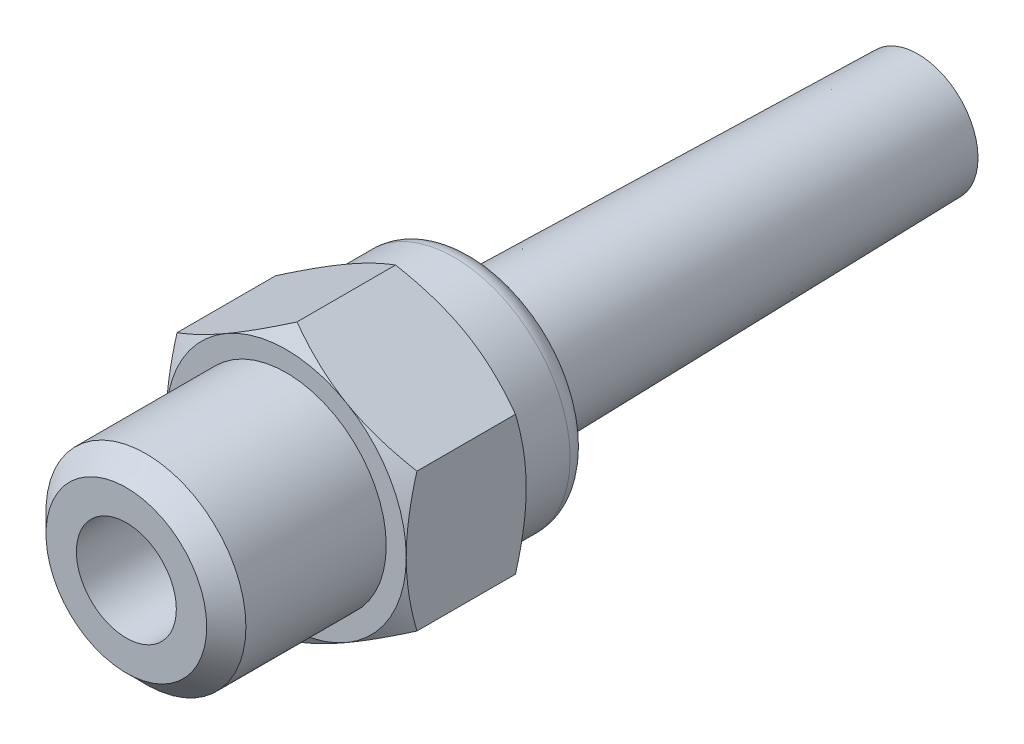
SolidWorks part; units mm, degrees
ref_plane "Ebene vorne" through (0, 0, 0) normal (0, 0, 1) x (1, 0, 0)
ref_plane "Ebene oben" through (0, 0, 0) normal (0, 1, 0) x (1, 0, 0)
ref_plane "Ebene rechts" through (0, 0, 0) normal (1, 0, 0) x (0, 0, -1)
sketch "Skizze1" plane through (0, 0, 0) normal (1, 0, 0) x (0, 0, -1)
  line L0 (4, 0) -> (4, 1.25)
  line L1 (4, 1.25) -> (0, 1.25)
  line L2 (0, 1.25) -> (0, 2.0095)
  line L3 (0, 2.0095) -> (0.4905, 2.5)
  line L4 (0.4905, 2.5) -> (4, 2.5)
  line L5 (4, 2.5) -> (4, 3)
  line L6 (4, 3) -> (4.3464, 3.6)
  line L7 (4.3464, 3.6) -> (6.6536, 3.6)
  line L8 (6.6536, 3.6) -> (7, 3)
  line L9 (7, 3) -> (7, 2.9)
  line L10 (7, 2.9) -> (8.2, 2.9)
  line L11 (8.7, 2.4) -> (8.7, 1.7415)
  line L12 (8.7, 1.7415) -> (19.8, 1.5)
  line L13 (19.8, 1.5) -> (19.8, 0)
  line L14 (19.8, 0) -> (4, 0)
  line L15 (19.8, 0) -> (0, 0) construction
  arc A0 (8.2, 2.9) -> (8.7, 2.4) centre (8.2, 2.4) cw
revolve "Rotation1" add sketch "Skizze1" angle 360 about L15 reverse direction yes
cosmetic thread "Gewindedarstellung1" parameters "D1"=4, "D2"=4.019
ref_plane "Ebene1" through (0, 0, -4) normal (0, 0, 1) x (1, 0, 0)
sketch "Skizze2" plane through (0, 0, -4) normal (0, 0, 1) x (1, 0, 0)
  line L0 (-6, 6) -> (-6, -6)
  line L1 (-6, -6) -> (6, -6)
  line L2 (6, -6) -> (6, 6)
  line L3 (6, 6) -> (-6, 6)
  line L4 (-3, -1.7321) -> (0, -3.4641)
  line L5 (0, -3.4641) -> (3, -1.7321)
  line L6 (3, -1.7321) -> (3, 1.7321)
  line L7 (3, 1.7321) -> (0, 3.4641)
  line L8 (0, 3.4641) -> (-3, 1.7321)
  line L9 (-3, 1.7321) -> (-3, -1.7321)
extrude "Schnitt-Linear austragen1" cut sketch "Skizze2" against normal blind 3
ref_plane "ANBAU XY" through (0, 0, -4) normal (0, 0, 1) x (1, 0, 0)
ref_plane "ANBAU XZ" through (0, 0, 0) normal (0, -1, 0) x (-1, 0, 0)
ref_plane "ANBAU YZ" through (0, 0, 0) normal (1, 0, 0) x (0, 0, -1)
ref_axis "ANBAU X" through (-80.9, 0, -4) along (1, 0, 0)
ref_axis "ANBAU Y" through (0, -50, -4) along (0, 1, 0)
ref_axis "ANBAU Z" through (0, 0, 80.9) along (0, 0, -1)
sketch3d "ANBAU"
  point P0 (0, 0, -4)
ref_plane "ANBAU_STD XY" through (0, 0, -4) normal (0, 0, -1) x (-1, 0, 0)
ref_plane "ANBAU_STD XZ" through (0, 0, 0) normal (0, 1, 0) x (1, 0, 0)
ref_plane "ANBAU_STD YZ" through (0, 0, 0) normal (1, 0, 0) x (0, 0, -1)
ref_axis "ANBAU_STD X" through (-80.9, 0, -4) along (1, 0, 0)
ref_axis "ANBAU_STD Y" through (0, 50, -4) along (0, -1, 0)
ref_axis "ANBAU_STD Z" through (0, 0, -80.9) along (0, 0, 1)
sketch3d "ANBAU_STD"
  point P0 (0, 0, -4)
